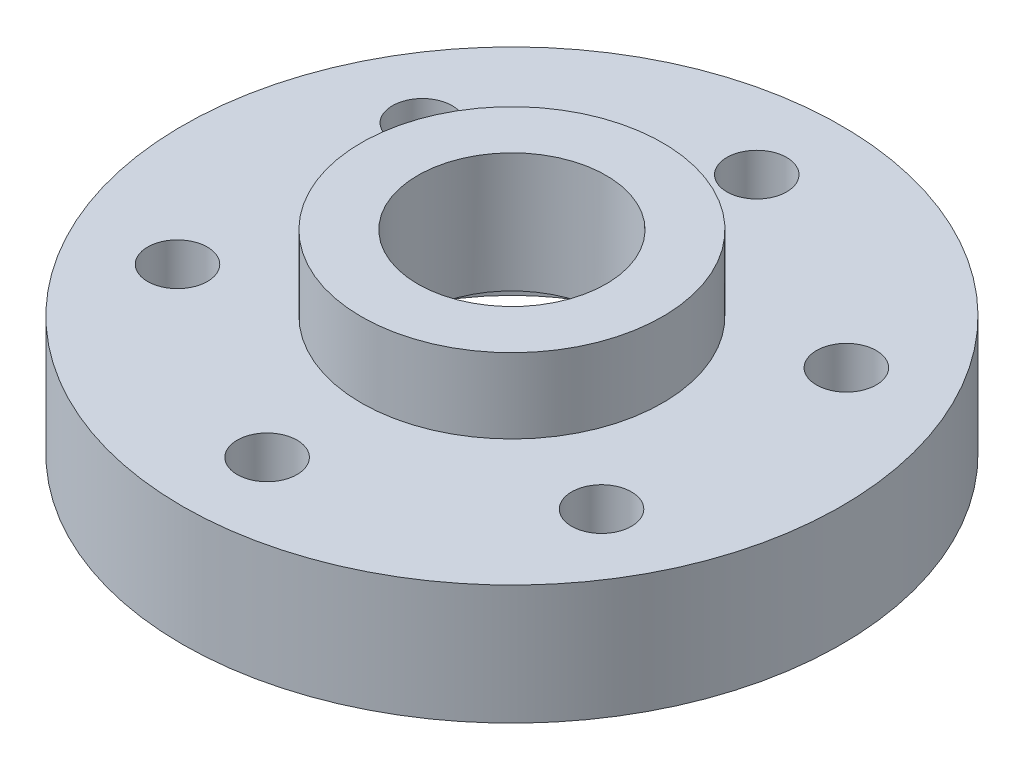
SolidWorks part; units mm, degrees
material "6061-T6 (SS)"
ref_plane "Front Plane" through (0, 0, 0) normal (0, 0, 1) x (1, 0, 0)
ref_plane "Top Plane" through (0, 0, 0) normal (0, 1, 0) x (1, 0, 0)
ref_plane "Right Plane" through (0, 0, 0) normal (1, 0, 0) x (0, 0, -1)
sketch "Sketch1" plane through (0, 0, 0) normal (0, 1, 0) x (1, 0, 0)
  circle A0 centre (0, 0) radius 35
  circle A1 centre (0, 0) radius 10
  dimension "D1" = 70
  dimension "D2" = 20
extrude "Boss-Extrude1" add sketch "Sketch1" against normal blind 12.7
sketch "Sketch2" plane through (0, 0, 0) normal (0, 1, 0) x (1, 0, 0)
  circle A0 centre (0, 0) radius 16
  circle A1 centre (0, 0) radius 10 construction
  circle A2 centre (0, 0) radius 10
  dimension "D1" = 32
extrude "Boss-Extrude2" add sketch "Sketch2" along normal blind 7.9375
sketch "Sketch3" plane through (0, -12.7, 0) normal (0, -1, 0) x (1, 0, 0)
  circle A0 centre (0, 0) radius 20.6375
  dimension "D1" = 41.275
extrude "Cut-Extrude1" cut sketch "Sketch3" against normal blind 7.9375
sketch "Sketch4" plane through (0, -12.7, 0) normal (0, -1, 0) x (1, 0, 0)
  circle A0 centre (0, 26) radius 3.175
  dimension "D2" = 6.35
  dimension "D1" = 26
extrude "Cut-Extrude2" cut sketch "Sketch4" against normal through all
pattern_circular "CirPattern1" count 6 over 360 about axis through (0, -12.7, 0) along (0, -1, 0) of "Cut-Extrude2"
equation "\"D1@Boss-Extrude2\"=0.375in-0.0625in"
equation "\"D2@Sketch4\"=0.25in"
